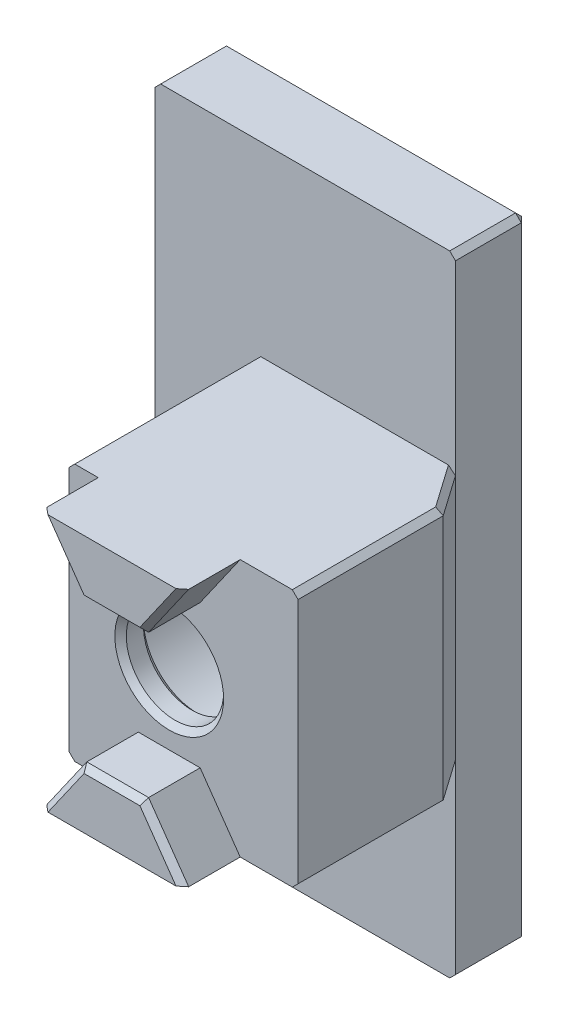
SolidWorks part; units mm, degrees
ref_plane "Front" through (0, 0, 0) normal (0, 0, 1) x (1, 0, 0)
ref_plane "Top" through (0, 0, 0) normal (0, 1, 0) x (1, 0, 0)
ref_plane "Right" through (0, 0, 0) normal (1, 0, 0) x (0, 0, -1)
sketch "Sketch1" plane through (0, 0, 0) normal (0, 0, 1) x (1, 0, 0)
  line L0 (7.5, -13.5) -> (7.5, -5) construction
  line L1 (0.5, -4.5) -> (7.5, -4.5)
  line L2 (0.5, -4.5) -> (0.5, 4.5)
  line L3 (0.5, 4.5) -> (7.5, 4.5)
  line L4 (7.5, -4.5) -> (7.5, 4.5) construction
  line L5 (0.5, -4.5) -> (7.5, 4.5) construction
  line L6 (0.5, 4.5) -> (7.5, -4.5) construction
  line L8 (7.5, 4.5) -> (8.5, 4.5)
  line L9 (8.5, 4.5) -> (8.5, -4.5)
  line L10 (8.5, -4.5) -> (7.5, -4.5)
  line L11 (0.5, 4.5) -> (0.5, -4.5) construction
  point P0 (4, 0)
extrude "Boss-Extrude1" add sketch "Sketch1" against normal blind 4
sketch "Sketch2" plane through (0, 0, 0) normal (0, 0, 1) x (1, 0, 0)
  line L46 (0.5, -4.5) -> (7.5, -4.5) construction
  line L48 (1.5199, -4.5) -> (6.4801, -4.5)
  line L67 (5.0797, -2.5) -> (2.9203, -2.5)
  line L68 (2.9203, -2.5) -> (1.3448, -4.75)
  line L69 (1.3448, -4.75) -> (2.9203, -7)
  line L70 (2.9203, -7) -> (5.0797, -7)
  line L71 (5.0797, -7) -> (6.6552, -4.75)
  line L72 (6.6552, -4.75) -> (5.0797, -2.5)
  line L73 (5.0797, -2.5) -> (2.9203, -2.5)
  line L74 (2.9203, -2.5) -> (1.5199, -4.5)
  line L78 (6.4801, -4.5) -> (5.0797, -2.5)
  dimension "D1" = 0.1
extrude "Slot Tab" add sketch "Sketch2" along normal blind 2 contours L48 L78 L73 L74 region at (4, -3.6311, 0)
mirror "Slot Tabs" about plane through (0, 0, 0) normal (0, 1, 0) of "Slot Tab"
sketch "Sketch7" plane through (0, 0, -4) normal (0, 0, -1) x (-1, 0, 0)
  point P0 (-4, 0)
hole_wizard "CBORE for M3 SHCS2" positions "Sketch7" profile "Sketch8" counterbore size "M3" standard "ANSI Metric" end condition through all
sketch "Sketch8" plane through (4, 0, -4) normal (1, 0, 0) x (0, 1, 0)
  line L0 (0, 0) -> (0, 6)
  line L1 (0, 6) -> (1.7, 6)
  line L3 (1.7, 6) -> (1.7, 3)
  line L4 (1.7, 3) -> (3.25, 3)
  line L5 (3.25, 3) -> (3.25, 0)
  line L7 (3.25, 0) -> (0, 0)
  line L11 (0, -6.35) -> (0, 107.95) construction
  dimension "Thru Hole Dia." = 3.4
  dimension "Thru Hole Depth" = 6
  dimension "C'Bore Dia." = 6.5
  dimension "C'Bore Depth" = 3
sketch "Sketch3" plane through (0, 0, -4) normal (0, 0, -1) x (-1, 0, 0)
  line L4 (-0.5, 4.5) -> (-8.5, 4.5)
  line L16 (-0.5, 4.5) -> (-8.5, 4.5)
  line L20 (-0.5, -4.5) -> (-0.5, 4.5)
  line L22 (-0.5, -4.5) -> (-0.5, 4.5)
  line L24 (-8.5, -4.5) -> (-0.5, -4.5)
  line L25 (-8.5, -4.5) -> (-0.5, -4.5)
  line L26 (-8.5, 4.5) -> (-8.5, -4.5)
  line L27 (-8.5, 4.5) -> (-8.5, -4.5)
  circle A0 centre (-4, 0) radius 3.25 construction
  circle A1 centre (-4, 0) radius 3.25
  dimension "D1" = 0
extrude "Stopper Clearance" add sketch "Sketch3" along normal blind 2.5
sketch "Sketch4" plane through (0, 0, -6.5) normal (0, 0, -1) x (-1, 0, 0)
  line L1 (-7.5, -11) -> (3, -11)
  line L2 (-7.5, -11) -> (-7.5, 11)
  line L3 (-7.5, 11) -> (3, 11)
  line L4 (3, -11) -> (3, 11)
  line L5 (-7.5, -11) -> (3, 11) construction
  line L6 (-7.5, 11) -> (3, -11) construction
  line L7 (-7.5, 13.5) -> (-7.5, 5) construction
  line L8 (3, 19.3) -> (3, -19.3) construction
  circle A0 centre (-4, 0) radius 3.25 construction
  circle A1 centre (-4, 0) radius 3.25
  point P0 (-2.25, 0)
  dimension "D2" = 22
extrude "Stopper" add sketch "Sketch4" along normal blind 2.5
chamfer "Deburs With Stopper" distance 0.2 angle 45 21 edges at (0.5, 4.5, -3.25) (0.5, -4.5, -3.25) (8.5, -4.5, -3.25) (8.5, 4.5, -3.25) (2.25, 11, -9) (7.5, 11, -7.75) (7.5, 0, -9) (-3, 11, -7.75) (-3, 0, -9) (-3, -11, -7.75) (2.25, -11, -9) (7.5, -11, -7.75) (5.7799, 3.5, 2) (4, 2.5, 2) (2.2201, 3.5, 2) (2.2201, -3.5, 2) (4, -2.5, 2) (5.7799, -3.5, 2) (0.75, 0, -9) (2.3, 0, 0) (2.3, 0, -1)
sketch "Sketch10" plane through (0, 0, 0) normal (0, 1, 0) x (1, 0, 0)
  line L0 (7.5, 6.5) -> (8.5, 6.5)
  line L1 (8.5, 6.5) -> (8.5, 5.0719)
  line L2 (8.5, 6.5) -> (8.5, 0) construction
  line L3 (8.5, 5.0719) -> (7.5, 6.5)
  dimension "D1" = 35
extrude "Print Chamfer" cut sketch "Sketch10" against normal through all both and the other way through all
chamfer "Chamfer5" distance 0.2 angle 45 2 edges at (7.9, 4.5, -5.9287) (7.9, -4.5, -5.9287)
chamfer "Deburs" [suppressed] distance 0.2 angle 45
